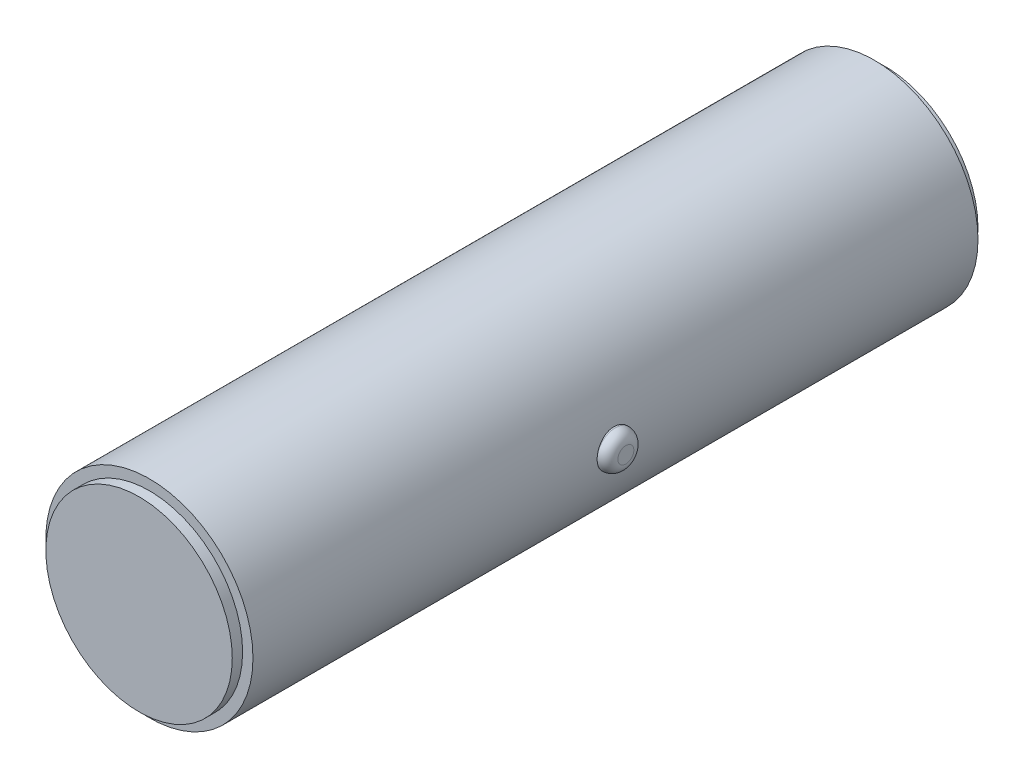
SolidWorks part; units mm, degrees
ref_plane "Front Plane" through (0, 0, 0) normal (0, 0, 1) x (1, 0, 0)
ref_plane "Top Plane" through (0, 0, 0) normal (0, 1, 0) x (1, 0, 0)
ref_plane "Right Plane" through (0, 0, 0) normal (1, 0, 0) x (0, 0, -1)
sketch "Sketch1" plane through (0, 0, 0) normal (0, 0, 1) x (1, 0, 0)
  circle A0 centre (0, 0) radius 2.5
  dimension "D1" = 5
extrude "Boss-Extrude1" add sketch "Sketch1" along normal blind 17.5
sketch "Sketch2" plane through (0, 0, 17.5) normal (0, 0, 1) x (1, 0, 0)
  circle A2 centre (0, 0) radius 2.25
  circle A3 centre (0, 0) radius 2.25
  dimension "D1" = 0.25
extrude "Boss-Extrude2" add sketch "Sketch2" along normal blind 0.25
sketch "Sketch3" plane through (0, 0, 0) normal (0, 0, -1) x (-1, 0, 0)
  circle A2 centre (0, 0) radius 2.25
  circle A3 centre (0, 0) radius 2.25
  dimension "D1" = 0.25
extrude "Boss-Extrude3" add sketch "Sketch3" along normal blind 0.25
sketch "Sketch4" plane through (0, 0, -0.25) normal (0, 0, -1) x (-1, 0, 0)
  circle A2 centre (0, 0) radius 0.25
  circle A3 centre (0, 0) radius 0.25
  dimension "D1" = 2
extrude "Boss-Extrude4" add sketch "Sketch4" along normal blind 1
sketch "Sketch5" plane through (0, 0, 0) normal (1, 0, 0) x (0, 0, -1)
  line L0 (0, 0) -> (-17.5, 0) construction
  line L1 (0, -2.5) -> (0, 2.5) construction
  line L2 (-17.5, 2.5) -> (-17.5, -2.5) construction
  circle A0 centre (-8.75, 0) radius 0.4426
extrude "Boss-Extrude5" add sketch "Sketch5" against normal blind 2.75 and the other way blind 2.75
fillet "Fillet1" radius 0.25 2 edges at (2.75, 0, 8.3074) (-2.75, 0, 8.3074)
